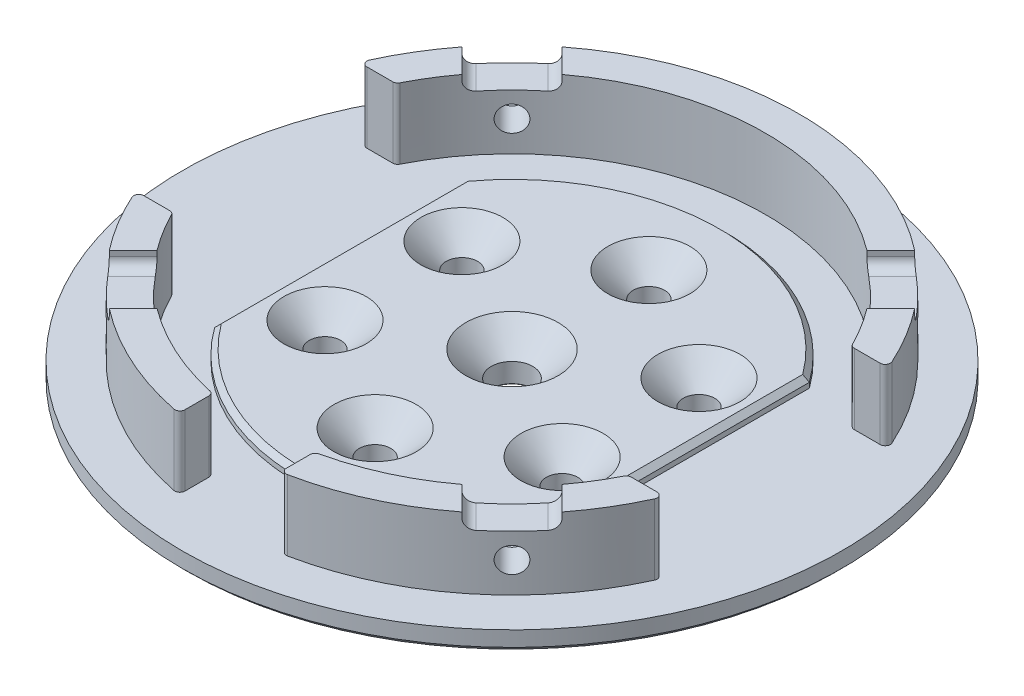
SolidWorks part; units mm, degrees
ref_plane "前视基准面" through (0, 0, 0) normal (0, 0, 1) x (1, 0, 0)
ref_plane "上视基准面" through (0, 0, 0) normal (0, 1, 0) x (1, 0, 0)
ref_plane "右视基准面" through (0, 0, 0) normal (1, 0, 0) x (0, 0, -1)
other "Configuration Table"
sketch "草图1" plane through (0, 0, 0) normal (0, 1, 0) x (1, 0, 0)
  circle A0 centre (0, 0) radius 32.5
  dimension "D1" = 65
extrude "凸台-拉伸1" add sketch "草图1" along normal blind 2
sketch "草图2" plane through (0, 2, 0) normal (0, 1, 0) x (1, 0, 0)
  line L0 (0, 25) -> (0, -25) construction
  line L1 (-25, 0) -> (25, 0) construction
  line L2 (-22.4499, 11) -> (-26.0747, 11)
  line L3 (-22.4499, -11) -> (-26.0747, -11)
  line L4 (22.4499, -11) -> (26.0747, -11)
  line L5 (22.4499, 11) -> (26.0747, 11)
  line L6 (-5, -24.4949) -> (-5, -27.8548)
  line L7 (5, -24.4949) -> (5, -27.8548)
  arc A0 (-26.0747, -11) -> (-5, -27.8548) centre (0, 0) ccw
  arc A1 (-22.4499, -11) -> (-5, -24.4949) centre (0, 0) ccw
  arc A2 (22.4499, 11) -> (-22.4499, 11) centre (0, 0) ccw
  arc A3 (26.0747, 11) -> (-26.0747, 11) centre (0, 0) ccw
  arc A4 (5, -24.4949) -> (22.4499, -11) centre (0, 0) ccw
  arc A5 (5, -27.8548) -> (26.0747, -11) centre (0, 0) ccw
  dimension "D1" = 56.6
  dimension "D2" = 50
  dimension "D3" = 11
  dimension "D4" = 5
extrude "凸台-拉伸2" add sketch "草图2" along normal blind 6.45
ref_axis "基准轴1" through (0, 8.45, 0) along (0, -1, 0)
ref_plane "基准面1" through (0, 0, 0) normal (0.7071, 0, 0.7071) x (0, -1, 0)
sketch "草图3" plane through (0, 0, 0) normal (0.7071, 0, 0.7071) x (0, -1, 0)
  line L0 (-8.45, 28.3) -> (-2, 28.3) construction
ref_plane "基准面2" through (20.0111, 0, -20.0111) normal (-0.7071, 0, 0.7071) x (0, -1, 0)
sketch "草图4" plane through (20.0111, 0, -20.0111) normal (-0.7071, 0, 0.7071) x (0, -1, 0)
  line L0 (-8.45, 0) -> (-2, 0) construction
  line L1 (2.75, 0) -> (-2.75, 0) construction
  line L2 (-2, 32.5) -> (-2, -32.5) construction
  circle A0 centre (-5, 0) radius 1.25
  dimension "D2" = 2.5
  dimension "D1" = 3
extrude "切除-拉伸1" cut sketch "草图4" along normal blind 4
pattern_circular "阵列(圆周)1" count 4 over 360 about axis through (0, 8.45, 0) along (0, -1, 0) of "切除-拉伸1"
sketch "草图5" plane through (0, 8.45, 0) normal (0, 1, 0) x (1, 0, 0)
  line L0 (-22.4499, -11) -> (-26.0747, -11) construction
  line L1 (-5, -27.8548) -> (-5, -24.4949) construction
  line L2 (5, -24.4949) -> (5, -27.8548)
  line L3 (26.0747, -11) -> (22.4499, -11)
  line L4 (5, -24.4949) -> (5, -27.8548)
  line L5 (26.0747, -11) -> (22.4499, -11)
  line L6 (22.4499, 11) -> (26.0747, 11) construction
  line L7 (-26.0747, 11) -> (-22.4499, 11) construction
  line L8 (-22.4499, -11) -> (-26.0747, -11)
  line L9 (-5, -27.8548) -> (-5, -24.4949)
  line L10 (22.4499, 11) -> (26.0747, 11)
  line L11 (-26.0747, 11) -> (-22.4499, 11)
  arc A0 (-22.4499, -11) -> (-5, -24.4949) centre (0, 0) ccw construction
  arc A1 (-26.0747, -11) -> (-5, -27.8548) centre (0, 0) ccw construction
  arc A2 (5, -24.4949) -> (22.4499, -11) centre (0, 0) ccw
  arc A3 (5, -27.8548) -> (26.0747, -11) centre (0, 0) ccw
  arc A4 (5, -24.4949) -> (22.4499, -11) centre (0, 0) ccw
  arc A5 (5, -27.8548) -> (26.0747, -11) centre (0, 0) ccw
  arc A6 (22.4499, 11) -> (-22.4499, 11) centre (0, 0) ccw construction
  arc A7 (26.0747, 11) -> (-26.0747, 11) centre (0, 0) ccw construction
  arc A8 (-22.4499, -11) -> (-5, -24.4949) centre (0, 0) ccw
  arc A9 (-26.0747, -11) -> (-5, -27.8548) centre (0, 0) ccw
  arc A10 (22.4499, 11) -> (-22.4499, 11) centre (0, 0) ccw
  arc A11 (26.0747, 11) -> (-26.0747, 11) centre (0, 0) ccw
  dimension "D1" = 0
extrude "凸台-拉伸3" add sketch "草图5" along normal blind 0.5
fillet "圆角1" radius 0.5 12 edges at (-5, 5.475, 27.8548) (-5, 5.475, 24.4949) (26.0747, 5.475, -11) (22.4499, 5.475, -11) (5, 5.475, 27.8548) (22.4499, 5.475, 11) (5, 5.475, 24.4949) (26.0747, 5.475, 11) (-22.4499, 5.475, 11) (-26.0747, 5.475, 11) (-22.4499, 5.475, -11) (-26.0747, 5.475, -11)
chamfer "倒角2" distance 0.5 angle 45 1 edges at (0, 0, 32.5)
sketch "草图7" plane through (0, 0, 0) normal (0, -1, 0) x (1, 0, 0)
  circle A0 centre (0, 0) radius 26
  dimension "D1" = 52
extrude "凸台-拉伸4" add sketch "草图7" along normal blind 1.5
sketch "草图8" plane through (0, -1.5, 0) normal (0, -1, 0) x (1, 0, 0)
  line L0 (0, 0) -> (0, 13.5) construction
  line L1 (0, 0) -> (0, 13.5) construction
  circle A6 centre (0, 0) radius 13.5 construction
  circle A7 centre (0, 0) radius 2.05
  circle A8 centre (0, 13.5) radius 1.55
  circle A11 centre (11.6913, 6.75) radius 1.55
  circle A12 centre (11.6913, -6.75) radius 1.55
  circle A13 centre (0, -13.5) radius 1.55
  circle A14 centre (-11.6913, -6.75) radius 1.55
  circle A21 centre (-11.6913, 6.75) radius 1.55
  point P19 (0, 0)
  dimension "D2" = 27
  dimension "D3" = 0
  dimension "D1" = 4.1
  dimension "D4" = 3.1
  dimension "D5" = 6
extrude "切除-拉伸2" cut sketch "草图8" against normal through all and the other way blind 9 contours A7 | A6 | A14 | A21 | A11 | A13 | A12 | A8 region at (0, -1.5, 0)
sketch "草图9" plane through (0, 2, 0) normal (0, 1, 0) x (1, 0, 0)
  line L0 (0, 0) -> (0, 13.5) construction
  line L1 (0, 0) -> (0, 13.5) construction
  circle A7 centre (0, 0) radius 2.05 construction
  circle A8 centre (0, 0) radius 21
  circle A22 centre (0, 0) radius 13.5 construction
  circle A29 centre (0, 0) radius 2.05
  circle A30 centre (-11.6913, 6.75) radius 1.55
  circle A31 centre (0, 13.5) radius 1.55
  circle A32 centre (11.6913, 6.75) radius 1.55
  circle A33 centre (11.6913, -6.75) radius 1.55
  circle A34 centre (0, -13.5) radius 1.55
  circle A35 centre (-11.6913, -6.75) radius 1.55
  point P32 (0, 0)
  point P41 (0, 0)
  dimension "D1" = 27
  dimension "D2" = 42
  dimension "D6" = 4.1
  dimension "D7" = 3.1
  dimension "D8" = 6
extrude "凸台-拉伸5" add sketch "草图9" along normal blind 1
chamfer "倒角4" distance 2.5 angle 45 7 edges at (0, 3, 2.05) (0, 3, 15.05) (11.6913, 3, 8.3) (11.6913, 3, -5.2) (0, 3, -11.95) (-11.6913, 3, -5.2) (-11.6913, 3, 8.3)
sketch "草图12" plane through (0, 3, 0) normal (0, 1, 0) x (1, 0, 0)
  line L0 (0, 29.459) -> (0, -25.1971) construction
  line L1 (-17, 12.3288) -> (-17, -12.3288)
  line L2 (17, 12.3288) -> (17, -12.3288)
  circle A0 centre (0, 0) radius 21 construction
  circle A1 centre (0, 0) radius 21 construction
  arc A2 (-17, 12.3288) -> (-17, -12.3288) centre (0, 0) ccw
  arc A3 (17, -12.3288) -> (17, 12.3288) centre (0, 0) ccw
  arc A4 (17, 12.3288) -> (17, -12.3288) centre (0, 0) cw
  circle M13 centre (0, 0) radius 21
  dimension "D1" = 17
extrude "切除-拉伸4" cut sketch "草图12" against normal blind 1 contours L2 M13 | L1 M13 region at (-18.6138, 3, 0) region at (18.6138, 3, 0)
chamfer "倒角5" distance 0.5 angle 45 5 edges at (0, -1.5, -26) (17, 3, 0) (0, 3, 21) (-17, 3, 0) (0, 3, -21)
sketch "草图14" plane through (20.0111, 0, -20.0111) normal (-0.7071, 0, 0.7071) x (0, -1, 0)
  line L0 (-8.95, 3.5) -> (-8.95, -3.5)
  line L1 (-8.95, -3.5) -> (-7.45, -3.5)
  line L2 (-7.45, -3.5) -> (-7.45, 3.5)
  line L3 (-7.45, 3.5) -> (-8.95, 3.5)
  line L4 (-8.95, 9.9407) -> (-8.95, -28.3) construction
  line L5 (-5, 0) -> (-12.9055, 0) construction
  dimension "D1" = 1.5
  dimension "D2" = 7
extrude "切除-拉伸5" cut sketch "草图14" along normal blind 6
pattern_circular "阵列(圆周)2" count 4 over 360 about axis through (0, 8.45, 0) along (0, -1, 0) of "切除-拉伸5"
fillet "圆角2" radius 1 8 edges at (16.2057, 7.45, 21.1554) (21.1554, 7.45, 16.2057) (16.2057, 7.45, -21.1554) (21.1554, 7.45, -16.2057) (-16.2057, 7.45, -21.1554) (-21.1554, 7.45, -16.2057) (-21.1554, 7.45, 16.2057) (-16.2057, 7.45, 21.1554)
chamfer "倒角6" distance 0.1 angle 45 7 edges at (0, -1.5, -15.05) (-11.6913, -1.5, -8.3) (-11.6913, -1.5, 5.2) (0, -1.5, -2.05) (0, -1.5, 11.95) (11.6913, -1.5, -8.3) (11.6913, -1.5, 5.2)
